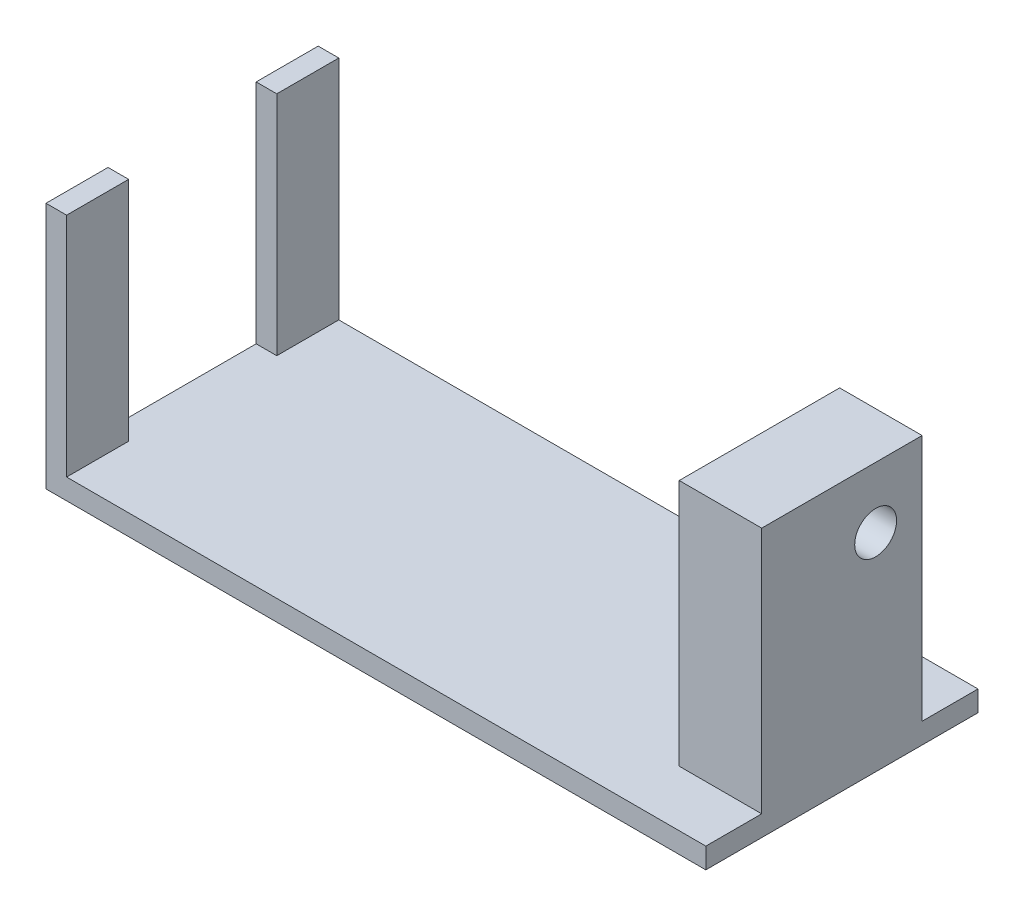
SolidWorks part; units mm, degrees
material "ABS"
ref_plane "Front Plane" through (0, 0, 0) normal (0, 0, 1) x (1, 0, 0)
ref_plane "Top Plane" through (0, 0, 0) normal (0, 1, 0) x (1, 0, 0)
ref_plane "Right Plane" through (0, 0, 0) normal (1, 0, 0) x (0, 0, -1)
sketch "Sketch2" plane through (0, 0, 0) normal (0, 1, 0) x (1, 0, 0)
  line L0 (0, 20.955) -> (0, 32.3596)
  line L13 (0, 0) -> (101.6, 0)
  line L14 (0, 0) -> (0, 41.91)
  line L15 (0, 41.91) -> (101.6, 41.91)
  line L16 (101.6, 0) -> (101.6, 41.91)
  line L17 (0, 20.955) -> (0, 9.5504)
  line L19 (0, 41.91) -> (3.175, 41.91)
  line L20 (0, 41.91) -> (0, 32.3596)
  line L21 (0, 32.3596) -> (3.175, 32.3596)
  line L22 (3.175, 41.91) -> (3.175, 32.3596)
  line L23 (0, 0) -> (3.175, 0)
  line L24 (0, 0) -> (0, 9.5504)
  line L25 (0, 9.5504) -> (3.175, 9.5504)
  line L26 (3.175, 0) -> (3.175, 9.5504)
  dimension "D1" = 101.6
  dimension "D2" = 41.91
  dimension "D3" = 11.4046
extrude "Boss-Extrude5" add sketch "Sketch2" along normal blind 38.1 contours L13 L26 L25 L14 | L22 L15 L14 L21 region at (1.5875, 0, -37.1348) region at (1.5875, 0, -4.7752)
extrude "Boss-Extrude6" add sketch "Sketch2<11>" along normal blind 3.175 contours L26 L13 L16 L15 L22 L21 L0 L14 L25 region at (51.511, 0, -20.955)
sketch "Sketch2<11>" plane through (0, 0, 0) normal (0, 1, 0) x (1, 0, 0) same geometry as "Sketch2"
ref_plane "Plane4" through (0, 3.175, 0) normal (0, 1, 0) x (1, 0, 0)
sketch "Sketch3" plane through (0, 3.175, 0) normal (0, 1, 0) x (1, 0, 0)
  line L0 (101.6, 20.955) -> (0, 20.955) construction
  line L1 (101.6, 0) -> (101.6, 41.91) construction
  line L2 (0, 9.5504) -> (0, 32.3596) construction
  line L4 (88.9, 33.3054) -> (101.6, 33.3054)
  line L5 (88.9, 33.3054) -> (88.9, 8.6046)
  line L6 (88.9, 8.6046) -> (101.6, 8.6046)
  line L7 (101.6, 33.3054) -> (101.6, 8.6046)
  line L8 (88.9, 33.3054) -> (101.6, 8.6046) construction
  line L9 (88.9, 8.6046) -> (101.6, 33.3054) construction
  point P6 (95.25, 20.955)
  dimension "D1" = 12.7
extrude "Boss-Extrude7" add sketch "Sketch3" along normal blind 38.1
ref_plane "Plane5" through (88.9, 0, 0) normal (-1, 0, 0) x (0, 0, 1)
sketch "Sketch4" plane through (88.9, 0, 0) normal (-1, 0, 0) x (0, 0, 1)
  line L0 (-33.3054, 41.275) -> (-33.3054, 3.175) construction
  line L3 (-33.3054, 3.175) -> (-8.6046, 3.175) construction
  circle A0 centre (-26.1502, 31.9024) radius 3.2258
  dimension "D1" = 6.4516
  dimension "D2" = 7.1552
  dimension "D3" = 28.7274
extrude "Cut-Extrude1" cut sketch "Sketch4" against normal blind 30.48
